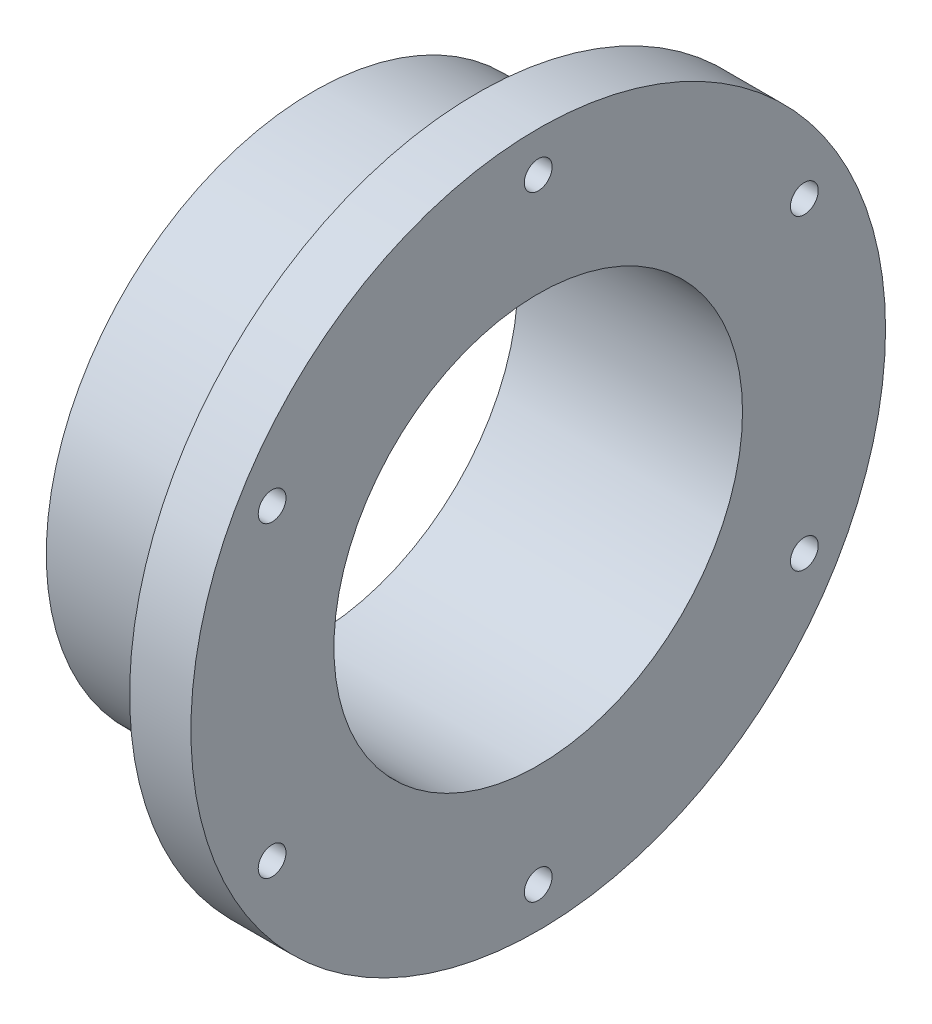
SolidWorks part; units mm, degrees
material "6063-T5"
ref_plane "Front" through (0, 0, 0) normal (0, 0, 1) x (1, 0, 0)
ref_plane "Top" through (0, 0, 0) normal (0, 1, 0) x (1, 0, 0)
ref_plane "Right" through (0, 0, 0) normal (1, 0, 0) x (0, 0, -1)
sketch "Croquis1" plane through (0, 0, 0) normal (1, 0, 0) x (0, 0, -1)
  circle A0 centre (0, 0) radius 32.7
  circle A1 centre (0, 0) radius 25
  dimension "D1" = 65.4
  dimension "D2" = 50
extrude "Saliente-Extruir1" add sketch "Croquis1" along normal mid plane 5
sketch "Croquis2" plane through (0, 0, 0) normal (1, 0, 0) x (0, 0, -1)
  circle A2 centre (0, 0) radius 25
  circle A3 centre (0, 0) radius 32.7
  dimension "D1" = 50
  dimension "D2" = 65.4
extrude "Saliente-Extruir2" add sketch "Croquis2" along normal blind 25
sketch "Croquis5" plane through (25, 0, 0) normal (1, 0, 0) x (0, 0, -1)
  circle A0 centre (0, 0) radius 42.5
  circle A2 centre (0, 0) radius 32.7
  circle A3 centre (0, 0) radius 32.7 construction
  dimension "D1" = 85
extrude "Saliente-Extruir4" add sketch "Croquis5" against normal blind 7.5
hole_wizard "Taladro de margen para M31" positions "Croquis8" profile "Croquis9" hole size "M3" standard "Ansi Metric" end condition up to next
sketch "Croquis8" plane through (17.5, 0, 0) normal (-1, 0, 0) x (0, 0, 1)
  line L0 (0, -15.125) -> (0, 15.125) construction
  line L1 (0, 42.5) -> (0, 32.7) construction
  circle A0 centre (0, 0) radius 42.5 construction
  circle A1 centre (0, 0) radius 32.7 construction
  point P0 (0, 37.6)
  point P17 (0, 37.6)
  point P22 (32.5626, 18.8)
  point P23 (32.5626, -18.8)
  point P24 (0, -37.6)
  point P25 (-32.5626, -18.8)
  point P26 (-32.5626, 18.8)
  point P29 (-58.8994, -44.1232)
  point P30 (0, 36.7352)
  point P32 (0, 0)
  dimension "D2" = 37.6
  dimension "D3" = 37.6
  dimension "D1" = 6
sketch "Croquis9" plane through (17.5, 37.6, 0) normal (0, 1, 0) x (0, 0, 1)
  line L0 (0, 0) -> (0, 7.5)
  line L1 (0, 7.5) -> (1.7, 7.5)
  line L2 (1.7, 7.5) -> (1.7, 0)
  line L5 (1.7, 0) -> (0, 0)
  line L11 (0, -6.35) -> (0, 107.95) construction
  dimension "Diámetro de taladro hasta el siguiente" = 3.4
  dimension "Profundidad de taladro hasta el siguiente" = 7.5
hole_wizard "Taladro de margen para M32" positions "Croquis10" profile "Croquis12" hole size "M3" standard "Ansi Metric"
sketch "Croquis10" plane through (-2.5, 0, 0) normal (-1, 0, 0) x (0, 0, 1)
  line L0 (0, -15.125) -> (0, 15.125) construction
  line L1 (15.125, 0) -> (-15.125, 0) construction
  point P0 (0, 28)
  point P11 (24.2487, 14)
  point P12 (24.2487, -14)
  point P13 (0, -28)
  point P15 (-24.2487, -14)
  point P16 (-24.2487, 14)
  dimension "D1" = 28
  dimension "D3" = 28
  dimension "D2" = 6
sketch "Croquis12" plane through (-2.5, 28, 0) normal (0, 1, 0) x (0, 0, 1)
  line L0 (0, 0) -> (0, 11.0215)
  line L1 (0, 11.0215) -> (1.7, 10)
  line L2 (1.7, 10) -> (1.7, 0)
  line L5 (1.7, 0) -> (0, 0)
  line L10 (0, 11.0215) -> (-1.7, 10) construction
  line L11 (0, -6.35) -> (0, 107.95) construction
  dimension "Diámetro de taladro" = 3.4
  dimension "Profundidad de taladro" = 10
  dimension "Ángulo de perforador" = 118
